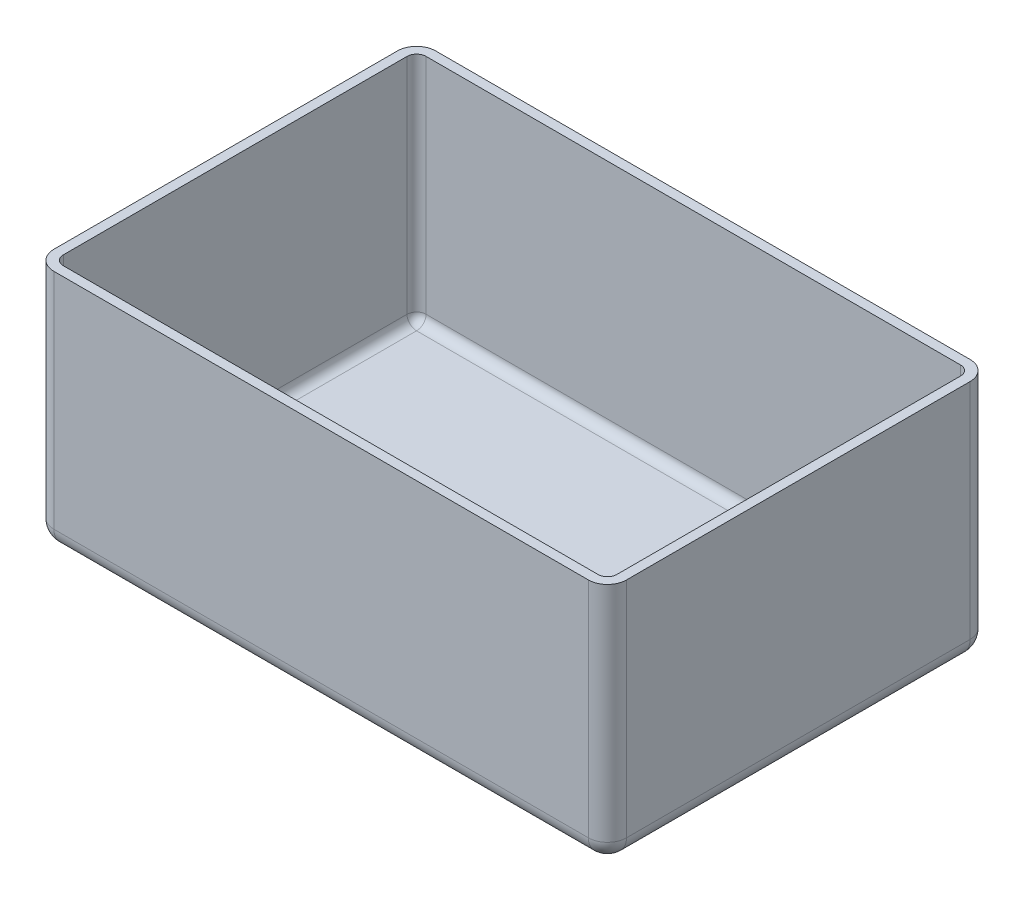
SolidWorks part; units mm, degrees
ref_plane "Front Plane" through (0, 0, 0) normal (0, 0, 1) x (1, 0, 0)
ref_plane "Top Plane" through (0, 0, 0) normal (0, 1, 0) x (1, 0, 0)
ref_plane "Right Plane" through (0, 0, 0) normal (1, 0, 0) x (0, 0, -1)
sketch "Sketch1" plane through (0, 0, 0) normal (0, 1, 0) x (1, 0, 0)
  line L1 (150, -100) -> (-150, -100)
  line L2 (150, -100) -> (150, 100)
  line L3 (150, 100) -> (-150, 100)
  line L4 (-150, -100) -> (-150, 100)
  line L5 (150, -100) -> (-150, 100) construction
  line L6 (150, 100) -> (-150, -100) construction
  point P0 (0, 0)
  dimension "D1" = 300
  dimension "D2" = 200
extrude "Boss-Extrude1" add sketch "Sketch1" along normal blind 127 contours L2 L1 L4 L3
fillet "Fillet1" radius 10 8 edges at (-150, 0, 0) (0, 0, 100) (150, 0, 0) (0, 0, -100) (150, 63.5, 100) (150, 63.5, -100) (-150, 63.5, -100) (-150, 63.5, 100)
shell "Shell1" thickness 5 removed face at (0, 127, 0)
